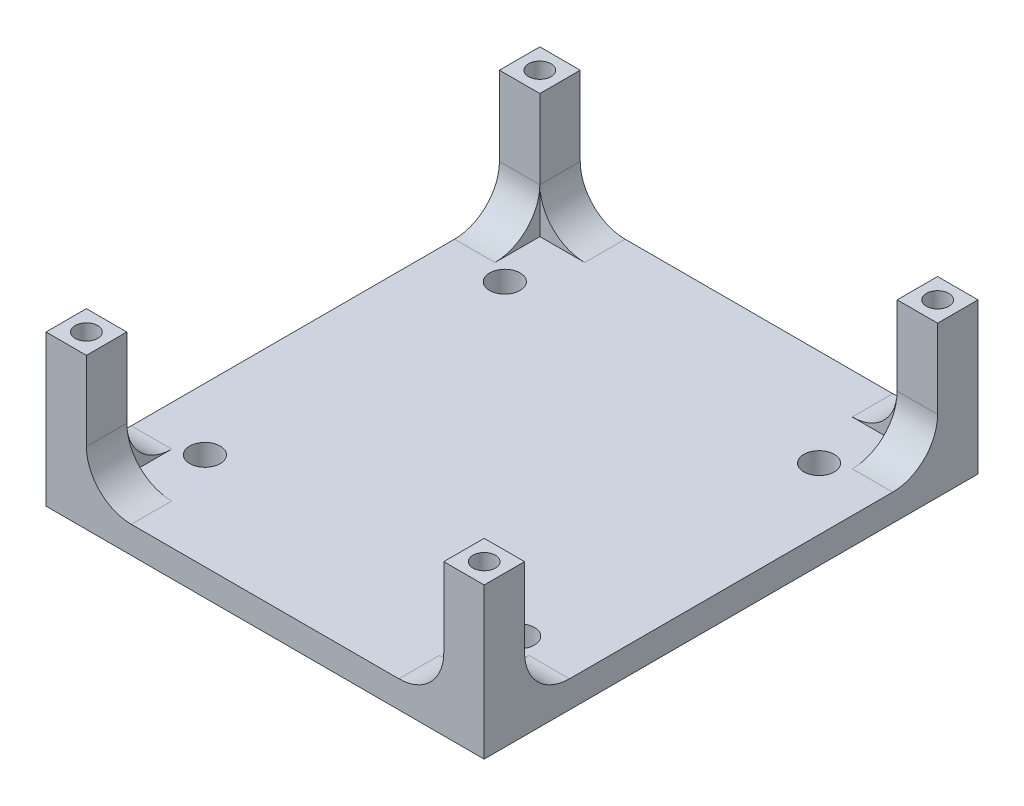
SolidWorks part; units mm, degrees
ref_plane "Front Plane" through (0, 0, 0) normal (0, 0, 1) x (1, 0, 0)
ref_plane "Top Plane" through (0, 0, 0) normal (0, 1, 0) x (1, 0, 0)
ref_plane "Right Plane" through (0, 0, 0) normal (1, 0, 0) x (0, 0, -1)
sketch "Sketch1" plane through (0, 0, 0) normal (0, 1, 0) x (1, 0, 0)
  line L0 (-17.5, 27.5) -> (-17.5, 16.7) construction
  line L1 (-24.4, -27.5) -> (24.4, -27.5)
  line L2 (-24.4, -27.5) -> (-24.4, 27.5)
  line L3 (-24.4, 27.5) -> (24.4, 27.5)
  line L4 (24.4, -27.5) -> (24.4, 27.5)
  line L5 (-24.4, -27.5) -> (24.4, 27.5) construction
  line L6 (-24.4, 27.5) -> (24.4, -27.5) construction
  line L7 (-17.5, 16.7) -> (-24.4, 16.7) construction
  point P0 (0, 0)
  dimension "D1" = 55
  dimension "D2" = 48.8
  dimension "D3" = 10.8
  dimension "D4" = 6.9
extrude "Boss-Extrude1" add sketch "Sketch1" along normal blind 3 contours L3 L4 L1 L2
sketch "Sketch2" plane through (0, 3, 0) normal (0, 1, 0) x (1, 0, 0)
  line L1 (-24.4, 27.5) -> (-19.9, 27.5)
  line L2 (-24.4, 27.5) -> (-24.4, 23)
  line L3 (-24.4, 23) -> (-19.9, 23)
  line L4 (-19.9, 27.5) -> (-19.9, 23)
  dimension "D1" = 4.5
extrude "Boss-Extrude2" add sketch "Sketch2" along normal blind 13.8
sketch "Sketch3" plane through (0, 16.8, 0) normal (0, 1, 0) x (1, 0, 0)
  line L0 (-22.15, 27.5) -> (-22.15, 23) construction
  line L1 (-19.9, 27.5) -> (-24.4, 27.5) construction
  line L2 (-24.4, 23) -> (-19.9, 23) construction
hole_wizard "M3x0.5 Tapped Hole1" positions "Sketch9" profile "Sketch11" tap size "M3x0.5" standard "ANSI Metric"
sketch "Sketch9" plane through (0, 16.8, 0) normal (0, 1, 0) x (1, 0, 0)
  line L0 (-22.15, 27.5) -> (-22.15, 23) construction
  point P0 (-22.15, 25.25)
sketch "Sketch11" plane through (-22.15, 16.8, -25.25) normal (1, 0, 0) x (0, 0, 1)
  line L0 (0, 0) -> (0, 7.7511)
  line L1 (0, 7.7511) -> (1.25, 7)
  line L2 (1.25, 7) -> (1.25, 0)
  line L5 (1.25, 0) -> (0, 0)
  line L10 (0, 7.7511) -> (-1.25, 7) construction
  line L11 (0, -6.35) -> (0, 107.95) construction
  dimension "Tap Drill Dia." = 2.5
  dimension "Tap Drill Depth" = 7
  dimension "Drill Angle" = 118
cosmetic thread "Hole Thread1" parameters "D1"=6, "D2"=3
hole_wizard "M3 Clearance Hole1" positions "Sketch12" profile "Sketch13" hole size "M3" standard "ANSI Metric"
sketch "Sketch12" plane through (0, 3, 0) normal (0, 1, 0) x (1, 0, 0)
  point P0 (-17.5, 16.7)
sketch "Sketch13" plane through (-17.5, 3, -16.7) normal (1, 0, 0) x (0, 0, 1)
  line L0 (0, 0) -> (0, 9.5215)
  line L1 (0, 9.5215) -> (1.7, 8.5)
  line L2 (1.7, 8.5) -> (1.7, 0)
  line L5 (1.7, 0) -> (0, 0)
  line L10 (0, 9.5215) -> (-1.7, 8.5) construction
  line L11 (0, -6.35) -> (0, 107.95) construction
  dimension "Hole Dia." = 3.4
  dimension "Hole Depth" = 8.5
  dimension "Drill Angle" = 118
fillet "Fillet1" radius 5 1 edges at (-22.15, 3, -23)
fillet "Fillet2" radius 5 1 edges at (-19.9, 3, -22.75)
mirror "Mirror3" about plane through (0, 0, 0) normal (1, 0, 0) of "M3 Clearance Hole1", "M3x0.5 Tapped Hole1", "Boss-Extrude2"
cosmetic thread "Hole Thread2" parameters "D1"=6, "D2"=3
mirror "Mirror4" about plane through (0, 0, 0) normal (0, 0, 1) of "Mirror3"
cosmetic thread "Hole Thread3" parameters "D1"=6, "D2"=3
cosmetic thread "Hole Thread4" parameters "D1"=6, "D2"=3
fillet "Fillet3" radius 5 1 edges at (22.15, 3, -23)
fillet "Fillet4" radius 5 1 edges at (19.9, 3, -22.75)
fillet "Fillet5" radius 5 1 edges at (22.15, 3, 23)
fillet "Fillet6" radius 5 1 edges at (19.9, 3, 22.75)
fillet "Fillet7" radius 5 1 edges at (-22.15, 3, 23)
fillet "Fillet8" radius 5 1 edges at (-19.9, 3, 22.75)
sketch "Sketch14" plane through (0, 3, 0) normal (0, 1, 0) x (1, 0, 0)
  line L1 (-19.4, -15) -> (19.4, -15)
  line L2 (-19.4, -15) -> (-19.4, 15)
  line L3 (-19.4, 15) -> (19.4, 15)
  line L4 (19.4, -15) -> (19.4, 15)
  line L5 (-19.4, -15) -> (19.4, 15) construction
  line L6 (-19.4, 15) -> (19.4, -15) construction
  point P0 (0, 0)
  dimension "D1" = 38.8
  dimension "D2" = 30
equation "\"W\"=45"
equation "\"H\"= 20"
equation "\"L\"= 38.8"
equation "\"d\"= 3.8"
equation "\"O\"= 5"
equation "\"D1@Sketch1\"=\"W\"+\"O\"*2"
equation "\"D2@Sketch1\"=\"L\"+2*\"O\""
equation "\"D1@Sketch14\"=\"L\""
equation "\"D2@Sketch14\"=\"W\" - 3*\"O\""
